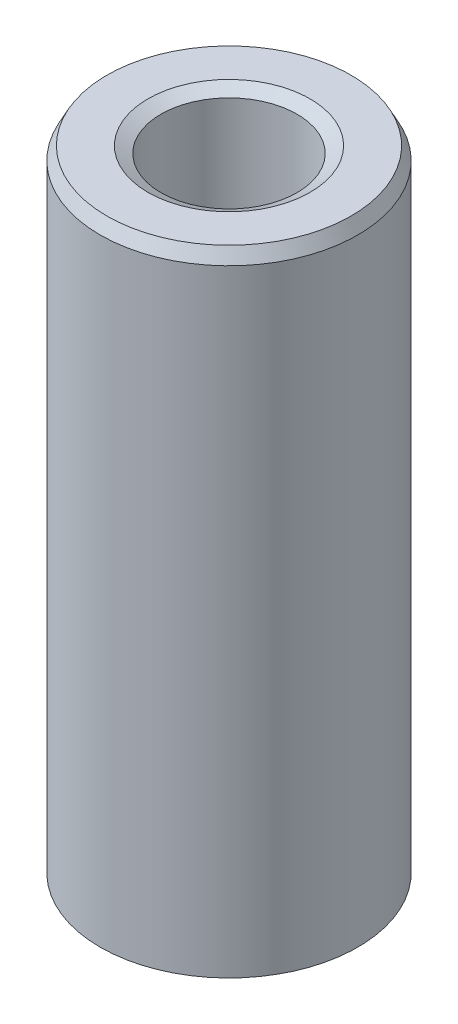
SolidWorks part; units mm, degrees
ref_plane "Front Plane" through (0, 0, 0) normal (0, 0, 1) x (1, 0, 0)
ref_plane "Top Plane" through (0, 0, 0) normal (0, 1, 0) x (1, 0, 0)
ref_plane "Right Plane" through (0, 0, 0) normal (1, 0, 0) x (0, 0, -1)
sketch "Sketch1" plane through (0, 0, 0) normal (0, 1, 0) x (1, 0, 0)
  circle A0 centre (0, 0) radius 5
  dimension "SLEEVE_OD" = 10
extrude "Boss-Extrude1" add sketch "Sketch1" along normal blind 24.7066
sketch "Sketch2" plane through (0, 0, 0) normal (0, 1, 0) x (1, 0, 0)
  circle A0 centre (0, 0) radius 2.641
  dimension "BORE_D" = 5.2821
extrude "Cut-Extrude1" cut sketch "Sketch2" along normal through all
chamfer "Chamfer1" distance 0.5052 angle 27.469 4 edges at (0, 24.7066, 2.641) (0, 0, 2.641) (0, 0, 5) (0, 24.7066, 5) first distance on face at (0, 24.7066, 2.641) first distance on face at (0, 0, 2.641) first distance on face at (0, 24.7066, 5)
